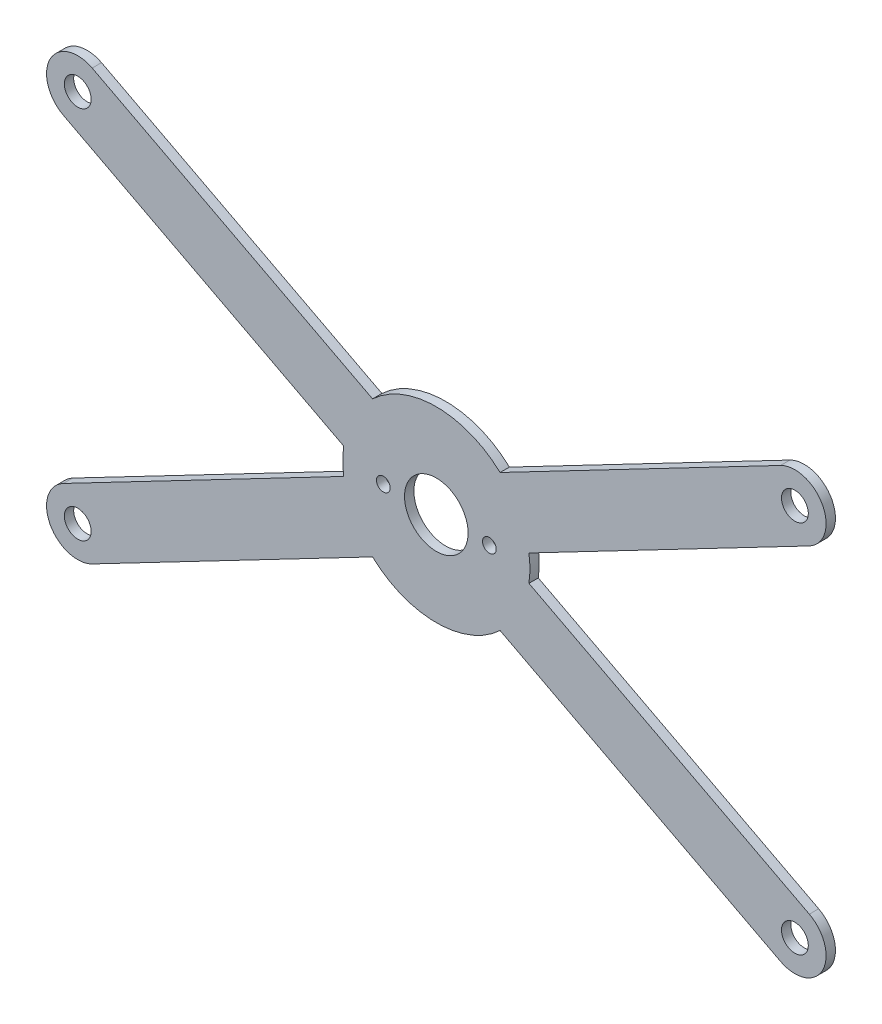
SolidWorks part; units mm, degrees
material "5052-H34"
ref_plane "正面" through (0, 0, 0) normal (0, 0, 1) x (1, 0, 0)
ref_plane "平面" through (0, 0, 0) normal (0, 1, 0) x (1, 0, 0)
ref_plane "右側面" through (0, 0, 0) normal (1, 0, 0) x (0, 0, -1)
sketch "ｽｹｯﾁ1" plane through (0, 0, 0) normal (0, 0, 1) x (1, 0, 0)
  line L0 (0, 0) -> (8.5, 0) construction
  line L1 (0, 0) -> (0, 23.4785) construction
  line L2 (10.2254, 10.9746) -> (55.1872, 34.4329)
  line L3 (-57.5, 30) -> (57.5, 30) construction
  line L4 (-57.5, 30) -> (-57.5, -30) construction
  line L5 (-57.5, -30) -> (-52.5, -30) construction
  line L6 (57.5, 30) -> (57.5, -30) construction
  line L7 (-57.5, 30) -> (57.5, -30) construction
  line L8 (-57.5, -30) -> (57.5, 30) construction
  line L9 (14.851, 2.1087) -> (59.8128, 25.5671)
  line L10 (-14.851, 2.1087) -> (-59.8128, 25.5671)
  line L11 (-10.2254, 10.9746) -> (-55.1872, 34.4329)
  line L12 (-14.851, -2.1087) -> (-59.8128, -25.5671)
  line L13 (-10.2254, -10.9746) -> (-55.1872, -34.4329)
  line L14 (10.2254, -10.9746) -> (55.1872, -34.4329)
  line L15 (14.851, -2.1087) -> (59.8128, -25.5671)
  line L16 (-52.5, -30) -> (-46.6907, -30) construction
  line L17 (-46.6907, -30) -> (57.5, -30) construction
  circle A0 centre (0, 0) radius 5.1
  circle A1 centre (8.5, 0) radius 1.1
  circle A2 centre (-8.5, 0) radius 1.1
  circle A3 centre (57.5, 30) radius 2.15
  circle A4 centre (57.5, -30) radius 2.15
  circle A5 centre (-57.5, -30) radius 2.15
  circle A6 centre (-57.5, 30) radius 2.15
  arc A7 (-14.851, 2.1087) -> (-14.851, -2.1087) centre (0, 0) ccw
  arc A8 (59.8128, 25.5671) -> (55.1872, 34.4329) centre (57.5, 30) ccw
  arc A9 (-59.8128, 25.5671) -> (-55.1872, 34.4329) centre (-57.5, 30) cw
  arc A10 (-59.8128, -25.5671) -> (-55.1872, -34.4329) centre (-57.5, -30) ccw
  arc A11 (59.8128, -25.5671) -> (55.1872, -34.4329) centre (57.5, -30) cw
  arc A12 (-52.5, 30) -> (-53.0671, 27.6872) centre (-57.5, 30) cw construction
  arc A13 (-55.1872, 34.4329) -> (-52.5, 30) centre (-57.5, 30) cw construction
  arc A14 (-53.0671, 27.6872) -> (-57.5, 25) centre (-57.5, 30) cw construction
  arc A15 (-57.5, 25) -> (-59.8128, 25.5671) centre (-57.5, 30) cw construction
  arc A16 (-13.2988, 6.9385) -> (-14.851, 2.1087) centre (0, 0) ccw construction
  arc A17 (-10.2254, 10.9746) -> (-13.2988, 6.9385) centre (0, 0) ccw construction
  arc A18 (13.2988, 6.9385) -> (10.2254, 10.9746) centre (0, 0) ccw construction
  arc A19 (10.2254, 10.9746) -> (-10.2254, 10.9746) centre (0, 0) ccw
  arc A20 (14.851, 2.1087) -> (13.2988, 6.9385) centre (0, 0) ccw construction
  arc A21 (53.0671, 27.6872) -> (57.5, 25) centre (57.5, 30) ccw construction
  arc A22 (52.5, 30) -> (53.0671, 27.6872) centre (57.5, 30) ccw construction
  arc A23 (55.1872, 34.4329) -> (52.5, 30) centre (57.5, 30) ccw construction
  arc A24 (57.5, 25) -> (59.8128, 25.5671) centre (57.5, 30) ccw construction
  arc A25 (10.2254, -10.9746) -> (13.2988, -6.9385) centre (0, 0) ccw construction
  arc A26 (14.851, -2.1087) -> (14.851, 2.1087) centre (0, 0) ccw
  arc A27 (13.2988, -6.9385) -> (14.851, -2.1087) centre (0, 0) ccw construction
  arc A28 (55.1872, -34.4329) -> (52.5, -30) centre (57.5, -30) cw construction
  arc A29 (52.5, -30) -> (53.0671, -27.6872) centre (57.5, -30) cw construction
  arc A30 (53.0671, -27.6872) -> (57.5, -25) centre (57.5, -30) cw construction
  arc A31 (57.5, -25) -> (59.8128, -25.5671) centre (57.5, -30) cw construction
  arc A32 (-13.2988, -6.9385) -> (-10.2254, -10.9746) centre (0, 0) ccw construction
  arc A33 (-10.2254, -10.9746) -> (10.2254, -10.9746) centre (0, 0) ccw
  arc A34 (-14.851, -2.1087) -> (-13.2988, -6.9385) centre (0, 0) ccw construction
  arc A35 (-53.0671, -27.6872) -> (-57.5, -25) centre (-57.5, -30) ccw construction
  arc A36 (-55.1872, -34.4329) -> (-52.5, -30) centre (-57.5, -30) ccw construction
  arc A37 (-52.5, -30) -> (-53.0671, -27.6872) centre (-57.5, -30) ccw
  arc A38 (-57.5, -25) -> (-59.8128, -25.5671) centre (-57.5, -30) ccw construction
  dimension "D1" = 10.2
  dimension "D2" = 2.2
  dimension "D6" = 4.3
  dimension "D7" = 30
  dimension "D8" = 10
  dimension "D3" = 17
  dimension "D4" = 115
  dimension "D5" = 60
extrude "ﾎﾞｽ - 押し出し1" add sketch "ｽｹｯﾁ1" along normal blind 1.5 contours L13 A33 L14 A11 L15 A26 L9 A8 L2 A19 L11 A9 L10 A7 L12 A10 A6 A5 A2 A1 A0 A3 A4 region at (33.369, 21.4336, 0)
